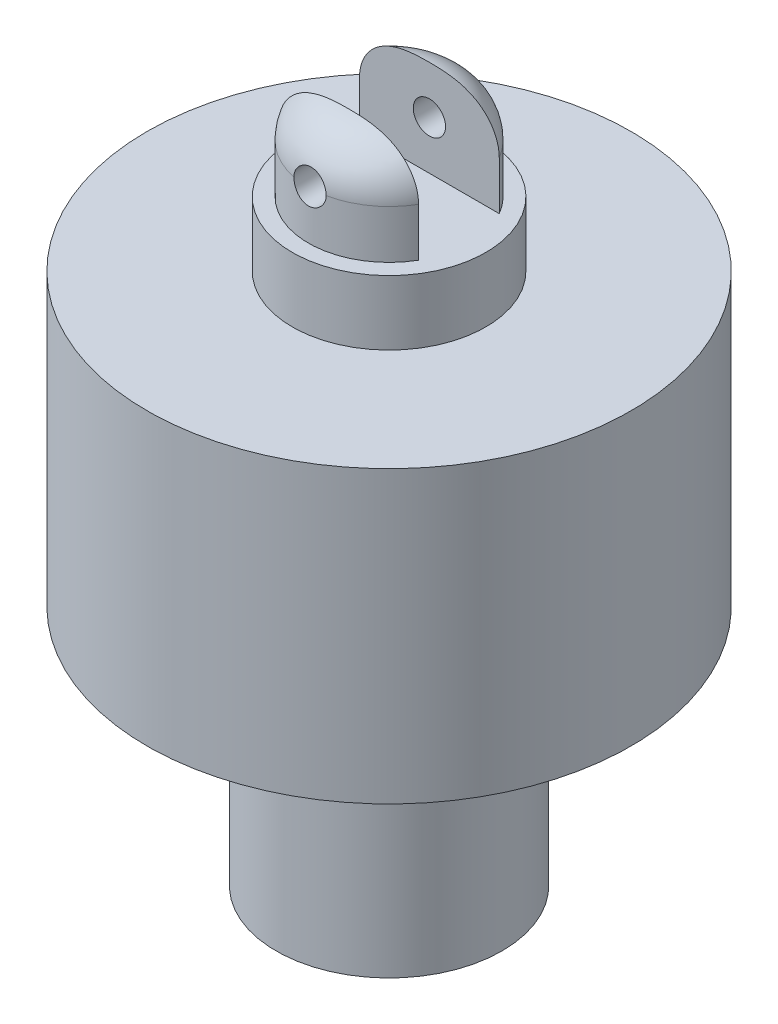
SolidWorks part; units mm, degrees
ref_plane "Front Plane" through (0, 0, 0) normal (0, 0, 1) x (1, 0, 0)
ref_plane "Top Plane" through (0, 0, 0) normal (0, 1, 0) x (1, 0, 0)
ref_plane "Right Plane" through (0, 0, 0) normal (1, 0, 0) x (0, 0, -1)
sketch "Sketch2" plane through (0, 0, 0) normal (0, 0, 1) x (1, 0, 0)
  line L0 (0, 37) -> (0, 0) construction
  line L2 (-4, 12) -> (-4, 15)
  line L3 (-4, 15) -> (-15, 15)
  line L4 (-15, 15) -> (-15, 33)
  line L5 (-15, 33) -> (-6, 33)
  line L6 (-6, 33) -> (-6, 37)
  line L7 (-6, 37) -> (-5, 37)
  line L8 (-5, 37) -> (-5, 43)
  line L9 (-5, 43) -> (0, 43)
  line L10 (0, 43) -> (0, 37)
  line L11 (-4, 12) -> (-7, 12)
  line L12 (-7, 12) -> (-7, 0)
  line L13 (-7, 0) -> (0, 0) construction
  line L15 (-7, 0) -> (-1, 0)
  line L16 (-1, 0) -> (-1, 4)
  line L17 (-1, 4) -> (0, 4)
  line L19 (0, 37) -> (0, 4)
  point P1 (0, 40)
  dimension "D1" = 7
  dimension "D2" = 4
  dimension "D3" = 15
  dimension "D4" = 6
  dimension "D5" = 5
  dimension "D6" = 6
  dimension "D7" = 4
  dimension "D8" = 18
  dimension "D9" = 15
  dimension "D10" = 3
  dimension "D11" = 1
  dimension "D12" = 4
revolve "Revolve1" add sketch "Sketch2" angle 360 about L0
fillet "Fillet1" radius 3 1 edges at (-5, 43, 0)
sketch "Sketch3" plane through (0, 0, 0) normal (1, 0, 0) x (0, 0, -1)
  line L0 (2, 43) -> (-2, 43) construction
  line L1 (-2.5, 43) -> (2.5, 43)
  line L2 (-2.5, 43) -> (-2.5, 37)
  line L3 (-2.5, 37) -> (2.5, 37)
  line L4 (2.5, 43) -> (2.5, 37)
  line L5 (0, 33) -> (0, 43) construction
  line L6 (15, 33) -> (-15, 33) construction
  point P9 (0, 33)
  point P12 (0, 43)
  point P13 (0, 43)
  dimension "D1" = 5
  dimension "D2" = 6
extrude "Cut-Extrude1" cut sketch "Sketch3" against normal blind 10 and the other way blind 10
sketch "Sketch4" plane through (0, 0, 2.5) normal (0, 0, -1) x (-1, 0, 0)
  line L0 (4.3301, 40) -> (-4.3301, 40) construction
  circle A0 centre (0, 40) radius 1
  dimension "D1" = 2
extrude "Cut-Extrude2" cut sketch "Sketch4" against normal blind 10 and the other way blind 10
